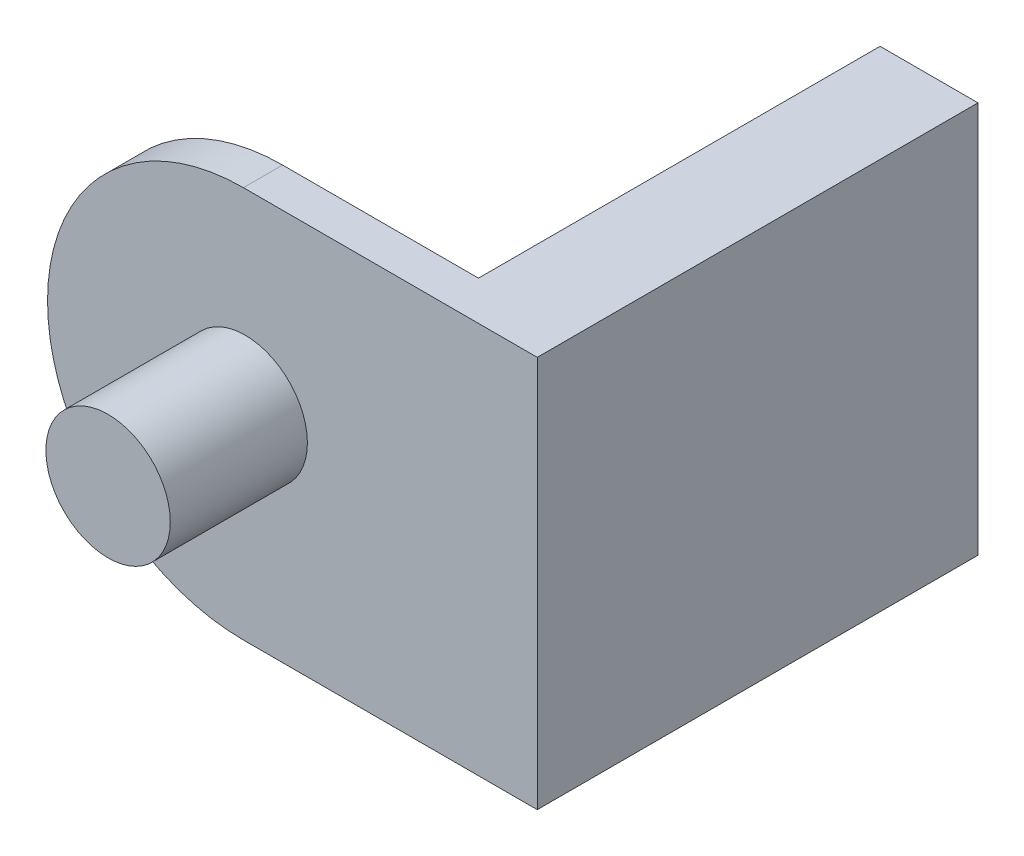
SolidWorks part; units mm, degrees
material "ABS"
ref_plane "Front" through (0, 0, 0) normal (0, 0, 1) x (1, 0, 0)
ref_plane "Top" through (0, 0, 0) normal (0, 1, 0) x (1, 0, 0)
ref_plane "Right" through (0, 0, 0) normal (1, 0, 0) x (0, 0, -1)
sketch "Esquisse1" plane through (0, 0, 0) normal (0, 0, 1) x (1, 0, 0)
  line L1 (-2.5, 10) -> (2.5, 10)
  line L2 (-2.5, 10) -> (-2.5, -10)
  line L3 (-2.5, -10) -> (2.5, -10)
  line L4 (2.5, 10) -> (2.5, -10)
  line L5 (-2.5, 10) -> (2.5, -10) construction
  line L6 (-2.5, -10) -> (2.5, 10) construction
  point P0 (0, 0)
  dimension "D1" = 5
  dimension "D2" = 20
extrude "Boss.-Extru.1" add sketch "Esquisse1" along normal blind 20.5
sketch "Esquisse2" plane through (0, 0, 20.5) normal (0, 0, 1) x (1, 0, 0)
  line L0 (-2.5, -10) -> (2.5, -10) construction
  line L1 (2.5, 10) -> (-22.5, 10)
  line L2 (2.5, 10) -> (2.5, -10)
  line L3 (2.5, -10) -> (-22.5, -10)
  line L4 (-22.5, 10) -> (-22.5, -10)
  dimension "D1" = 25
extrude "Boss.-Extru.2" add sketch "Esquisse2" along normal blind 2
sketch "Esquisse3" plane through (0, 0, 22.5) normal (0, 0, 1) x (1, 0, 0)
  line L0 (2.5, 10) -> (-22.5, 10) construction
  line L2 (-2.5, 10) -> (-2.5, -10) construction
  circle A0 centre (-12.41, 0.35) radius 3.175
  dimension "D1" = 6.35
  dimension "D2" = 9.65
  dimension "D3" = 9.91
extrude "Boss.-Extru.3" add sketch "Esquisse3" along normal blind 7
fillet "Congé1" radius 10 2 edges at (-22.5, 10, 21.5) (-22.5, -10, 21.5)
sketch "Esquisse4" plane through (0, 0, 0) normal (0, 0, -1) x (-1, 0, 0)
  line L0 (-2.5, 10) -> (2.5, 10) construction
  line L1 (-2.5, -10) -> (-2.5, 10) construction
  circle A0 centre (0, 5) radius 1.05
  circle A1 centre (0, -5) radius 1.05
  point P8 (0, 0)
  dimension "D1" = 10
  dimension "D2" = 5
  dimension "D3" = 2.1
  dimension "D4" = 2.5
extrude "Enlèv. mat.-Extru.1" cut sketch "Esquisse4" against normal blind 8
